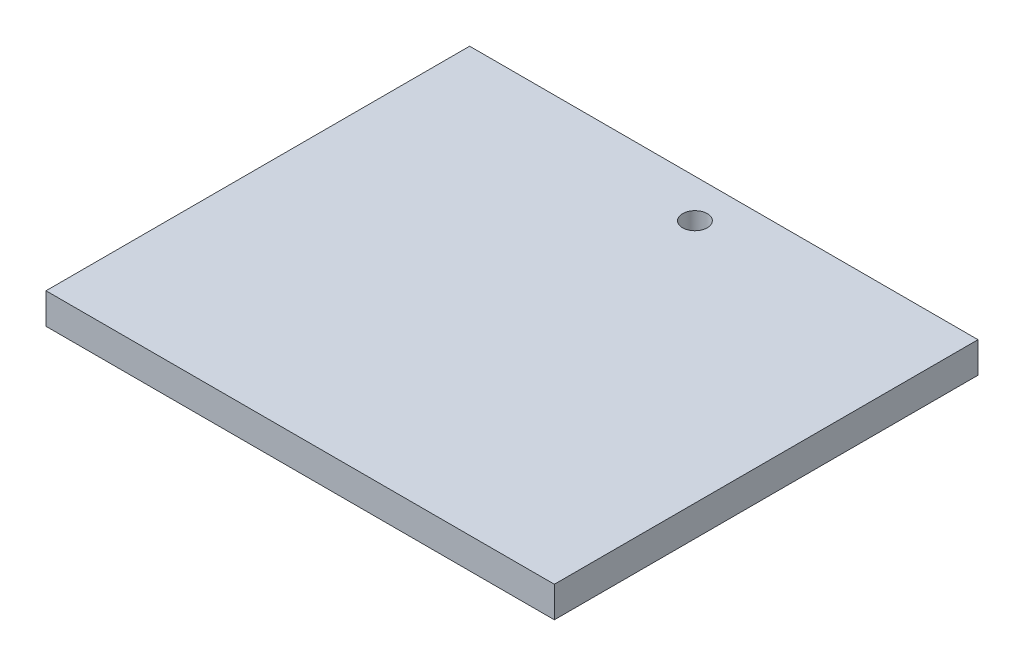
SolidWorks part; units mm, degrees
ref_plane "Front Plane" through (0, 0, 0) normal (0, 0, 1) x (1, 0, 0)
ref_plane "Top Plane" through (0, 0, 0) normal (0, 1, 0) x (1, 0, 0)
ref_plane "Right Plane" through (0, 0, 0) normal (1, 0, 0) x (0, 0, -1)
sketch "Sketch1" plane through (0, 0, 0) normal (0, 1, 0) x (1, 0, 0)
  line L0 (33, 27.5) -> (1.25, 27.5)
  line L1 (-33, 27.5) -> (33, 27.5)
  line L2 (-33, 27.5) -> (-33, -27.5)
  line L3 (-33, -27.5) -> (33, -27.5)
  line L4 (33, 27.5) -> (33, -27.5)
  line L5 (-33, 27.5) -> (33, -27.5) construction
  line L6 (-33, -27.5) -> (33, 27.5) construction
  line L7 (1.25, 27.5) -> (1.25, 22.5) construction
  circle A0 centre (1.25, 22.5) radius 1.6
  point P0 (0, 0)
  dimension "D5" = 3.2
  dimension "D1" = 66
  dimension "D2" = 55
  dimension "D3" = 31.75
  dimension "D4" = 5
extrude "Boss-Extrude1" add sketch "Sketch1" along normal blind 4 contours L4 L0 L1 L2 L3 A0 region at (-0.0028, 0, 0.05)
